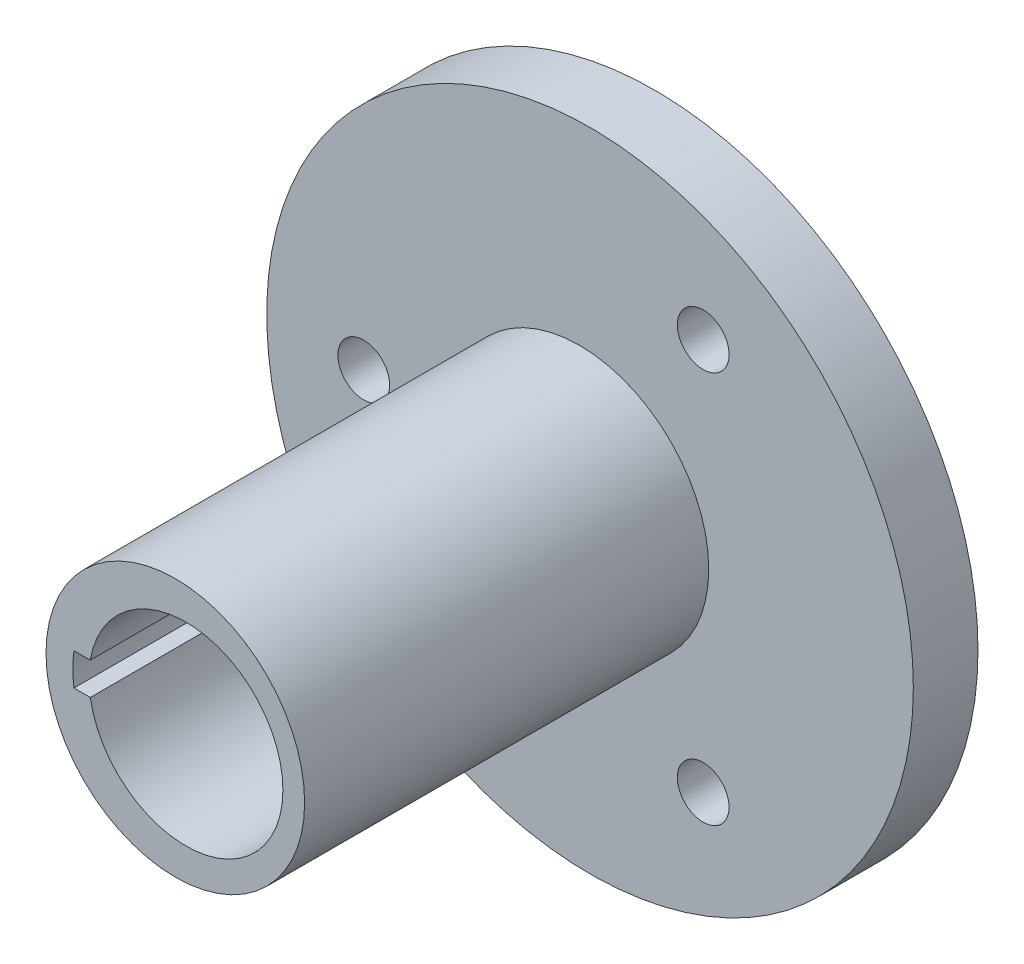
SolidWorks part; units mm, degrees
ref_plane "Front Plane" through (0, 0, 0) normal (0, 0, 1) x (1, 0, 0)
ref_plane "Top Plane" through (0, 0, 0) normal (0, 1, 0) x (1, 0, 0)
ref_plane "Right Plane" through (0, 0, 0) normal (1, 0, 0) x (0, 0, -1)
sketch "Sketch1" plane through (0, 0, 0) normal (0, 0, 1) x (1, 0, 0)
  line L0 (0, 0) -> (-58.2991, 0) construction
  line L1 (-14.7902, 2.5) -> (-17.3205, 2.5)
  line L2 (-14.7902, -2.5) -> (-17.3205, -2.5)
  circle A0 centre (0, 0) radius 50
  arc A1 (-14.7902, -2.5) -> (-14.7902, 2.5) centre (0, 0) ccw
  arc A2 (-17.3205, 2.5) -> (-17.3205, -2.5) centre (0, 0) ccw
  circle A3 centre (0, 0) radius 17.5 construction
  circle A4 centre (0, 0) radius 15 construction
  circle A5 centre (0, 0) radius 35
  circle A6 centre (-35, 0) radius 4
  circle A7 centre (17.5, 30.3109) radius 4
  circle A8 centre (17.5, -30.3109) radius 4
  circle A9 centre (-1.6409, 0) radius 20
  point P20 (0, 0)
  dimension "D1" = 100
  dimension "D2" = 30
  dimension "D4" = 3
  dimension "D3" = 2.5
extrude "Boss-Extrude1" add sketch "Sketch1" against normal blind 10 contours A0
extrude "Cut-Extrude1" cut sketch "Sketch1<3>" against normal blind 10 contours A6 | A7 | A8
sketch "Sketch1<3>" plane through (0, 0, 0) normal (0, 0, 1) x (1, 0, 0) same geometry as "Sketch1"
extrude "Boss-Extrude2" add sketch "Sketch1<4>" along normal blind 62.5 contours A9 A2 L1 A1 L2 region at (-21.0752, 0, 0)
sketch "Sketch1<4>" plane through (0, 0, 0) normal (0, 0, 1) x (1, 0, 0) same geometry as "Sketch1"
sketch "Sketch3" plane through (0, 0, 0) normal (0, 0, 1) x (1, 0, 0)
  circle A0 centre (0, 0) radius 6.5
sketch "Sketch4" plane through (0, 0, 0) normal (0, 0, 1) x (1, 0, 0)
  circle A0 centre (0, 0) radius 15
extrude "Cut-Extrude3" cut sketch "Sketch3" against normal through all both and the other way through all contours A0
sketch "Sketch5" plane through (0, 0, 0) normal (0, 0, 1) x (1, 0, 0)
  line L0 (0, 0) -> (-50, 0) construction
  circle A0 centre (0, 0) radius 50 construction
